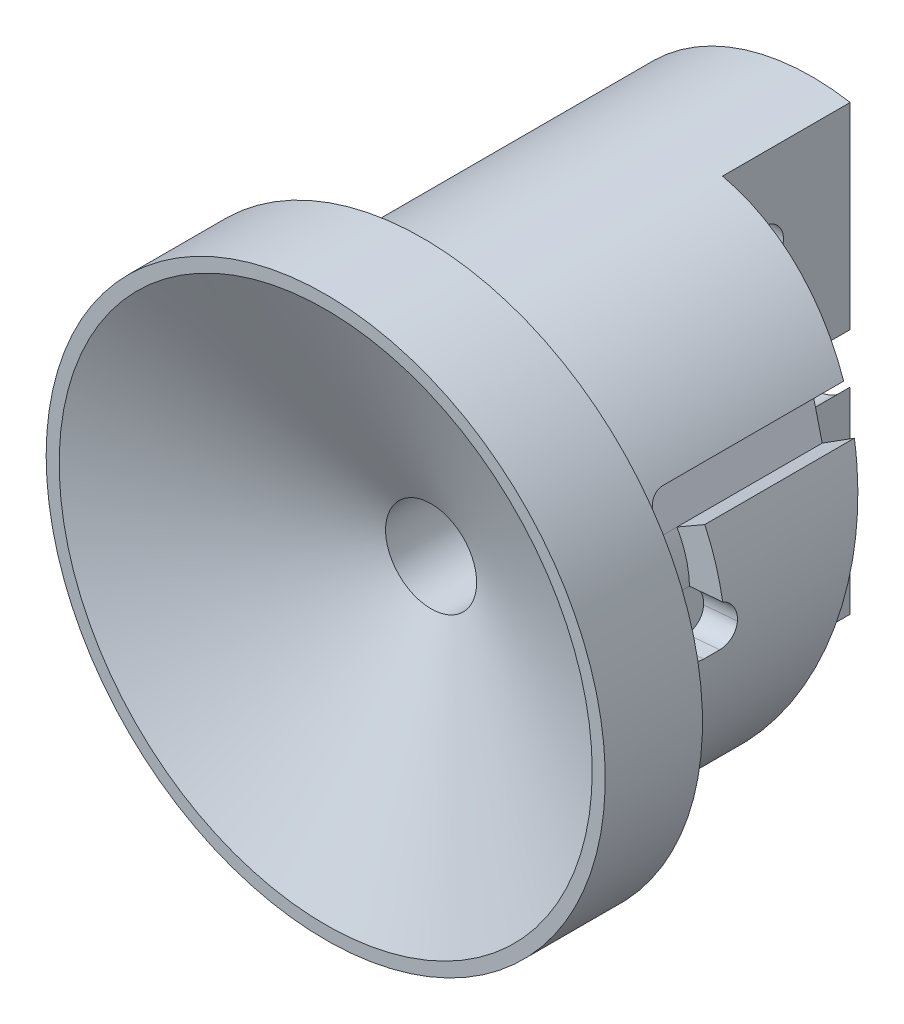
SolidWorks part; units mm, degrees
material "A-2 Steel"
ref_plane "Alzado" through (0, 0, 0) normal (0, 0, 1) x (1, 0, 0)
ref_plane "Planta" through (0, 0, 0) normal (0, 1, 0) x (1, 0, 0)
ref_plane "Vista lateral" through (0, 0, 0) normal (1, 0, 0) x (0, 0, -1)
sketch "Croquis2" plane through (0, 0, 0) normal (1, 0, 0) x (0, 0, -1)
  line L0 (0.3255, 0) -> (-7.0214, 0) construction
  line L1 (0, 2.9718) -> (31.75, 2.9718)
  line L2 (31.75, 2.9718) -> (31.75, 14.6812)
  line L3 (31.75, 14.6812) -> (6.35, 14.6812)
  line L4 (6.35, 14.6812) -> (6.35, 18.2499)
  line L5 (6.35, 18.2499) -> (0, 18.2499)
  line L6 (0, 18.2499) -> (0, 2.9718)
  dimension "D1" = 5.9436
  dimension "D2" = 36.4998
  dimension "D3" = 31.75
  dimension "D4" = 25.4
  dimension "D5" = 29.3624
revolve "Revolución1" add sketch "Croquis2" angle 360 about L0
sketch "Croquis3" plane through (0, 0, 0) normal (0, 1, 0) x (1, 0, 0)
  line L0 (0, 8.2982) -> (-17.399, 0)
  line L2 (-18.2499, 0) -> (18.2499, 0) construction
  line L3 (-17.399, 0) -> (0, 0)
  line L4 (0, 0) -> (0, 8.2982)
  line L5 (0, 0) -> (0, -3.613) construction
  dimension "D1" = 3.613
  dimension "D2" = 34.798
  dimension "D3" = 8.2982
revolve "Cortar-Revolución1" cut sketch "Croquis3" angle 360 about L5
sketch "Croquis4" plane through (0, 0, -31.75) normal (0, 0, -1) x (-1, 0, 0)
  line L0 (-2.4892, -14.4686) -> (-2.4892, 14.4686)
  circle A1 centre (0, 0) radius 14.6812 construction
  circle A3 centre (0, 0) radius 14.6812
  arc A4 (-2.4892, 14.4686) -> (-2.4892, -14.4686) centre (0, 0) ccw
  dimension "D1" = 2.4892
  dimension "D2" = 0
ref_plane "Plano1" through (2.4892, 0, 0) normal (-1, 0, 0) x (0, 1, 0)
sketch "Croquis5" plane through (2.4892, 0, 0) normal (-1, 0, 0) x (0, 1, 0)
  line L0 (14.4686, 23.4188) -> (-14.4686, 15.6651)
  line L1 (14.4686, 31.75) -> (-14.4686, 31.75) construction
  line L4 (-14.4686, 31.75) -> (-14.4686, 15.6651)
  line L6 (14.4686, 23.4188) -> (14.4686, 31.75)
  line L7 (-14.4686, 31.75) -> (14.4686, 31.75) construction
  line L8 (14.4686, 31.75) -> (-14.4686, 31.75)
  dimension "D1" = 15
  dimension "D2" = 8.3312
extrude "Cortar-Extruir1" cut sketch "Croquis5" against normal through all
hole_wizard "Taladro roscado #6-321" positions "Croquis6" profile "Croquis7" tap size "#6-32" standard "Ansi Inch"
sketch "Croquis6" plane through (2.4892, 0, 0) normal (1, 0, 0) x (0, 0, -1)
  line L0 (26.0398, 8.9408) -> (31.75, 8.9408) construction
  line L1 (31.75, -14.4686) -> (31.75, 14.4686) construction
  line L3 (0, 0) -> (31.75, 0) construction
  line L5 (19.9769, 1.6234) -> (23.4188, 14.4686) construction
  point P0 (26.0398, 8.9408)
  dimension "D1" = 8.9408
  dimension "D2" = 3.9624
sketch "Croquis7" plane through (2.4892, 8.9408, -26.0398) normal (0, 1, 0) x (0, 0, -1)
  line L0 (0, 0) -> (0, 11.7855)
  line L1 (0, 11.7855) -> (1.3525, 10.9728)
  line L2 (1.3525, 10.9728) -> (1.3525, 0)
  line L5 (1.3525, 0) -> (0, 0)
  line L10 (0, 11.7855) -> (-1.3526, 10.9728) construction
  line L11 (0, -6.35) -> (0, 107.95) construction
  dimension "Diámetro de perforador para roscar" = 2.7051
  dimension "Profundidad de perforador para roscar" = 10.9728
  dimension "Ángulo de perforador" = 118
cosmetic thread "Rosca de taladro1" parameters "D1"=7.0104, "D2"=3.5052
sketch "Croquis8" plane through (0, 0, -31.75) normal (0, 0, -1) x (-1, 0, 0)
  line L0 (-13.3178, 6.1786) -> (-11.4986, 5.1283)
  line L1 (-11.4986, 5.1283) -> (-10.1905, 7.3939)
  line L2 (-10.1905, 7.3939) -> (-12.0097, 8.4443)
  line L3 (0, 0) -> (-18.2499, 0) construction
  line L4 (0, 0) -> (-15.8049, 9.125) construction
  arc A0 (-2.4892, 14.4686) -> (-2.4892, -14.4686) centre (0, 0) ccw construction
  arc A1 (-12.0097, 8.4443) -> (-13.3178, 6.1786) centre (0, 0) ccw
  circle A2 centre (0, 0) radius 18.2499 construction
  point P12 (-10.8445, 6.2611)
  point P13 (-12.7143, 7.3406)
  dimension "D1" = 30
  dimension "D2" = 2.6162
  dimension "D3" = 2.159
extrude "Cortar-Extruir2" cut sketch "Croquis8" against normal offset from surface (22.9362 mm away) 2.4638 up to face at (-18.2499, 0, -6.35)
sketch "Croquis9" plane through (0, 0, -8.8138) normal (0, 0, -1) x (-1, 0, 0)
  line L0 (-10.8445, 6.2611) -> (0, 0) construction
  line L1 (-10.1905, 7.3939) -> (-11.4986, 5.1283) construction
  line L2 (0, 0) -> (-18.2499, 0) construction
  line L3 (0, 0) -> (-18.1805, 1.5906) construction
  line L5 (-12.3024, 2.3894) -> (-12.5304, -0.2168)
  line L6 (-12.5304, -0.2168) -> (-14.6812, -0.0287)
  line L7 (-11.0956, 5.8262) -> (-11.4986, 5.1283) construction
  line L8 (-11.0956, 5.8262) -> (-12.9579, 6.9014)
  circle A0 centre (0, 0) radius 18.2499 construction
  arc A1 (-13.3178, 6.1786) -> (-2.4892, -14.4686) centre (0, 0) ccw construction
  circle A2 centre (0, 0) radius 14.6812 construction
  arc A3 (-13.7662, 5.102) -> (-14.6812, -0.0287) centre (0, 0) ccw construction
  arc A4 (-11.0956, 5.8262) -> (-12.3024, 2.3894) centre (0, 0) ccw
  arc A5 (-12.9579, 6.9014) -> (-14.6812, -0.0287) centre (0, 0) ccw
  arc A6 (-12.0097, 8.4443) -> (-13.3178, 6.1786) centre (0, 0) ccw construction
  point P12 (-12.4164, 1.0863)
  point P15 (-14.4532, 2.5776)
  arc M11 (-12.0097, 8.4443) -> (-13.3178, 6.1786) centre (0, 0) ccw
  line M12 (-13.3178, 6.1786) -> (-11.4986, 5.1283)
  line M13 (-11.4986, 5.1283) -> (-10.1905, 7.3939)
  dimension "D1" = 25
  dimension "D2" = 2.6162
  dimension "D3" = 2.159
  dimension "D4" = 2.159
extrude "Cortar-Extruir3" cut sketch "Croquis9" along normal blind 2.6162 contours A5 L6 L5 A4 M12 M13 | L8 M13 M11 M12 region at (13.2214, 2.7992, -8.8138) region at (12.2183, 6.0109, -8.8138)
sketch "Croquis10" plane through (12.4164, 1.0863, 0) normal (0.9962, 0.0872, 0) x (0, 0, -1)
  line L0 (8.8138, 1.3081) -> (8.8138, -1.3081) construction
  line L1 (12.2428, -0.0974) -> (10.9347, -0.0974) construction
  line L3 (11.43, -1.3081) -> (11.43, 1.1133)
  arc A0 (11.43, -1.3081) -> (11.43, 1.1133) centre (10.9347, -0.0974) ccw
  dimension "D1" = 3.429
  dimension "D2" = 2.6162
extrude "Cortar-Extruir4" cut sketch "Croquis10" along normal through all
fillet "Redondeo1" radius 1.1938 2 edges at (11.1001, 7.9191, -8.8138) (13.6058, -0.1227, -8.8138)
sketch "Croquis11" plane through (0, 0, -11.43) normal (0, 0, 1) x (1, 0, 0)
  line L0 (10.1905, 7.3939) -> (11.4986, 5.1283) construction
  line L1 (11.0956, 5.8262) -> (11.4986, 5.1283)
  line L2 (12.5304, -0.2168) -> (12.3193, 2.1954) construction
  line L3 (12.3024, 2.3894) -> (12.3193, 2.1954)
  arc A0 (12.3193, 2.1954) -> (11.4986, 5.1283) centre (6.1834, 2.0595) ccw
  arc A10 (12.3024, 2.3894) -> (11.0956, 5.8262) centre (0, 0) ccw
  arc A11 (12.3024, 2.3894) -> (11.0956, 5.8262) centre (0, 0) ccw construction
extrude "Saliente-Extruir1" add sketch "Croquis11" along normal up to surface (2.6162 mm away) up to face at (12.3975, 4.0516, -8.8138)
fillet "Redondeo2" radius 1.1938 1 edges at (13.6058, -0.1227, -11.43)
